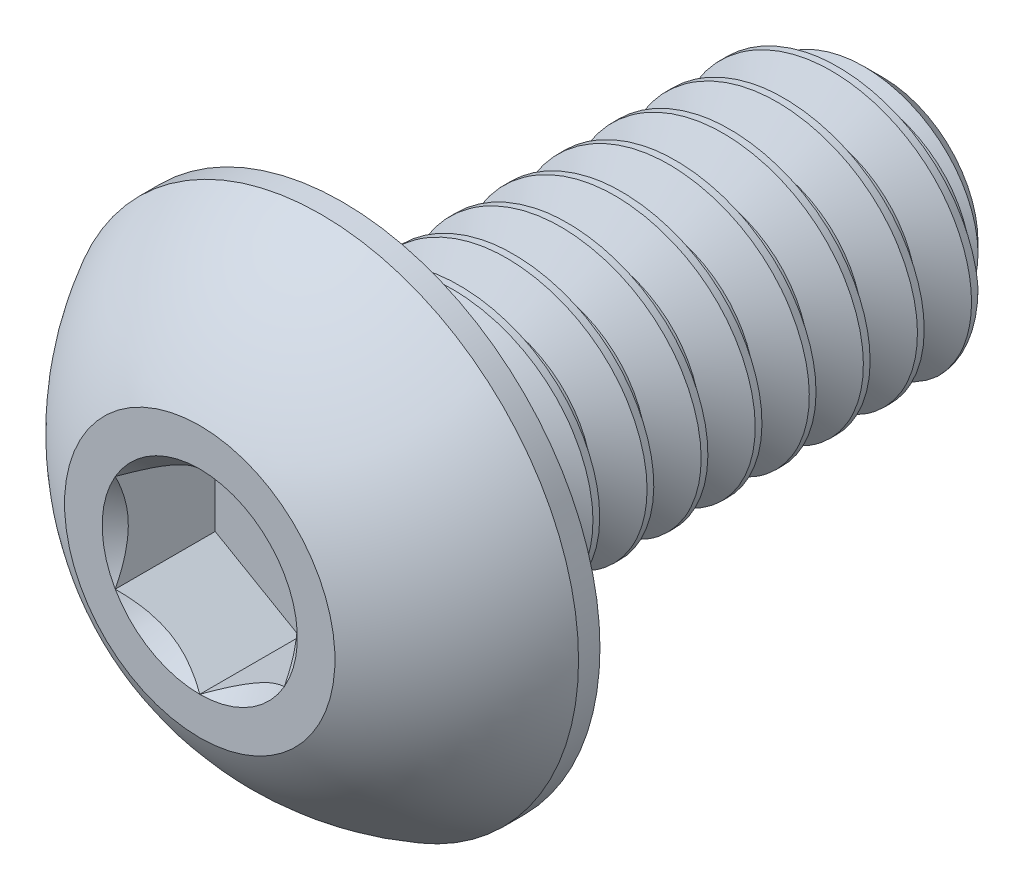
SolidWorks part; units mm, degrees
ref_plane "Front" through (0, 0, 0) normal (0, 0, 1) x (1, 0, 0)
ref_plane "Top" through (0, 0, 0) normal (0, 1, 0) x (1, 0, 0)
ref_plane "Right" through (0, 0, 0) normal (1, 0, 0) x (0, 0, -1)
sketch "Sketch1" plane through (0, 0, 0) normal (1, 0, 0) x (0, 0, -1)
  line L2 (1.6764, 1.5875) -> (8.0264, 1.5875)
  line L3 (8.0264, 1.5875) -> (8.0264, 0)
  line L4 (8.0264, 0) -> (1.6764, 0)
  line L6 (1.4249, 3.0226) -> (1.6764, 3.0226) construction
  line L7 (8.0264, 1.5875) -> (8.0264, -1.5875) construction
  line L8 (0, 0) -> (1.6764, 0) construction
  line L9 (1.6764, 3.0226) -> (1.6764, -3.0226) construction
  line L11 (1.6764, 1.5875) -> (1.6764, 0)
  line L13 (0, 0.9922) -> (0, -0.9922) construction
  line L14 (0, 0.9922) -> (0, 1.5875) construction
  arc A3 (0, 1.5875) -> (1.4249, 3.0226) centre (3.034, 0) cw construction
  dimension "D1" = 0.2515
  dimension "Head Ht" = 1.6764
  dimension "Head Dia" = 6.0452
  dimension "Dia" = 3.175
  dimension "Lg" = 6.35
  dimension "Hex" = 1.9844
revolve "Revolve1" add sketch "Sketch1" angle 360 about L4
sketch "Sketch3" plane through (0, 0, -8.0264) normal (0, 0, -1) x (-1, 0, 0)
  circle A0 centre (0, 0) radius 1.5875
curve "Helix/Spiral1" pitch 0.635 height 6.985 radius 1.5875 centre (0, 0, -8.0264) axis (0, 0, 1) start towards (0, 1, 0)
sketch "Sketch2" plane through (0, 0, 0) normal (1, 0, 0) x (0, 0, -1)
  line L0 (8.0264, 1.5875) -> (8.582, 1.5875)
  line L1 (8.582, 1.5875) -> (8.3439, 1.1751)
  line L2 (8.3439, 1.1751) -> (8.2645, 1.1751)
  line L3 (8.2645, 1.1751) -> (8.0264, 1.5875)
  line L4 (8.1455, 1.3813) -> (8.463, 1.3813) construction
  dimension "D1" = 60
  dimension "D2" = 0.0794
  dimension "D3" = 0.3175
chamfer "Chamfer1" distance 0.4763 angle 45 1 edges at (0, 1.5875, -8.0264)
sweep "Cut-Sweep1" cut profiles "Sketch2" path "Helix/Spiral1"
sketch "Sketch7" plane through (0, 0, 0) normal (1, 0, 0) x (0, 0, -1)
  line L6 (1.4249, 3.0226) -> (1.6764, 3.0226) construction
  line L8 (0, 0) -> (1.6764, 0) construction
  line L11 (1.6764, 3.0226) -> (1.6764, -3.0226) construction
  line L12 (1.4249, 3.0226) -> (1.6764, 3.0226)
  line L13 (0, 0) -> (1.6764, 0)
  line L14 (0, 0.9922) -> (0, -0.9922) construction
  line L15 (1.6764, 3.0226) -> (1.6764, 0)
  line L16 (0, 1.5875) -> (0, 0)
  arc A2 (1.4249, 3.0226) -> (0, 1.5875) centre (3.034, 0) ccw construction
  arc A3 (1.4249, 3.0226) -> (0, 1.5875) centre (3.034, 0) ccw
revolve "Revolve2" add sketch "Sketch7" angle 360 about L13
sketch "Sketch5" plane through (0, 0, 0) normal (0, 0, 1) x (1, 0, 0)
  line L1 (0.9922, -0.5728) -> (0.9922, 0.5728)
  line L2 (0.9922, 0.5728) -> (0, 1.1457)
  line L3 (0, 1.1457) -> (-0.9922, 0.5728)
  line L4 (-0.9922, 0.5728) -> (-0.9922, -0.5728)
  line L5 (-0.9922, -0.5728) -> (0, -1.1457)
  line L6 (0, -1.1457) -> (0.9922, -0.5728)
  circle A0 centre (0, 0) radius 0.9922 construction
extrude "Cut-Extrude2" cut sketch "Sketch5" against normal blind 1.1735
sketch "Sketch6" plane through (0, 0, 0) normal (0, 0, 1) x (1, 0, 0)
  circle A0 centre (0, 0) radius 1.1457
extrude "Cut-Extrude3" cut sketch "Sketch6" against normal blind 1.1735 draft 45
sketch "Sketch9" [suppressed] plane through (0, 0, -1.4986) normal (0, 0, 1) x (1, 0, 0)
  circle A2 centre (0, 0) radius 1.4224
extrude "Boss-Extrude2" [suppressed] add sketch "Sketch9" against normal offset from surface (12.7 mm away) 31.75 up to face at (0, 1.1113, -8.0264)
sketch "Sketch10" plane through (0, 0, 0) normal (1, 0, 0) x (0, 0, -1)
  line L0 (8.0264, 1.5875) -> (8.0264, -1.5875) construction
  point P0 (7.0739, -1.5875)
  dimension "D1" = 0.9525
equation "\"D3@Helix/Spiral1\" = \"Lg@Sketch1\" + \"D4@Helix/Spiral1\""
equation "\"D2@Sketch2\" = \"D4@Helix/Spiral1\" * .125"
equation "\"D3@Sketch2\" = \"D4@Helix/Spiral1\" * .5"
equation "\"D1@Chamfer1\" = \"D4@Helix/Spiral1\" * .75"
equation "\"D1@Cut-Extrude2\" = \"Head Ht@Sketch1\" * .7"
equation "\"D1@Sketch1\" = \"Head Ht@Sketch1\" * .15"
equation "\"D1@Sketch10\" = \"D4@Helix/Spiral1\" * 1.5"
equation "\"D1@Cut-Extrude3\" = \"D1@Cut-Extrude2\""
